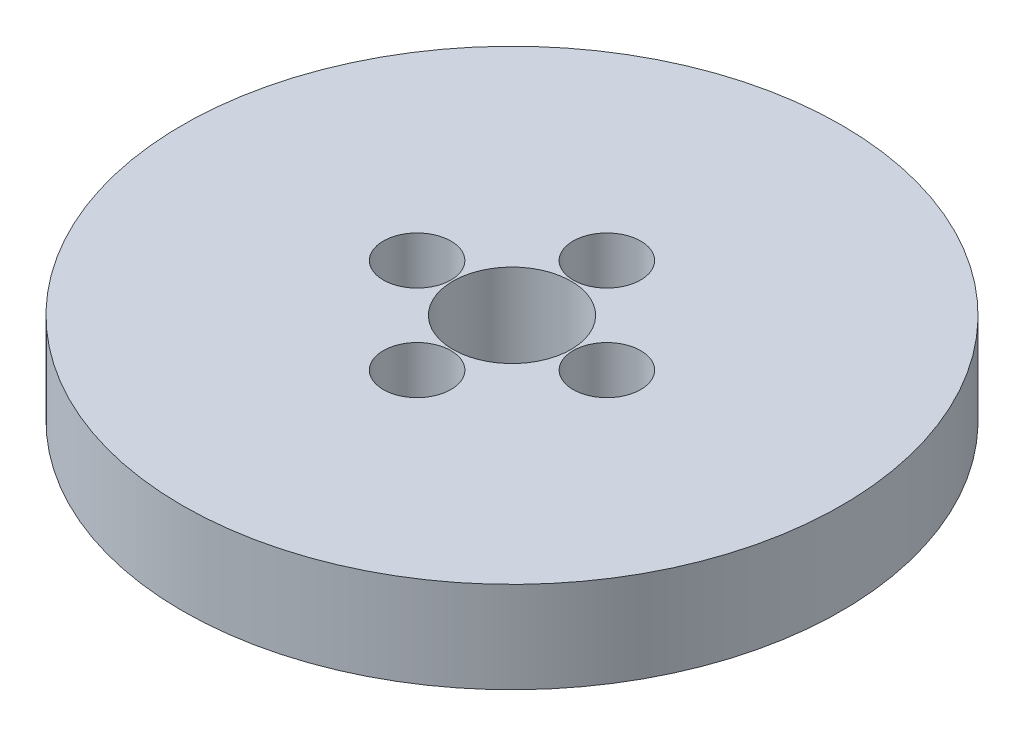
SolidWorks part; units mm, degrees
ref_plane "Front Plane" through (0, 0, 0) normal (0, 0, 1) x (1, 0, 0)
ref_plane "Top Plane" through (0, 0, 0) normal (0, 1, 0) x (1, 0, 0)
ref_plane "Right Plane" through (0, 0, 0) normal (1, 0, 0) x (0, 0, -1)
sketch "Sketch1" plane through (0, 0, 0) normal (0, 1, 0) x (1, 0, 0)
  circle A0 centre (0, 0) radius 97.5
  dimension "FLANGE_OD" = 195
extrude "Boss-Extrude1" add sketch "Sketch1" along normal blind 27
sketch "Sketch2" plane through (0, 0, 0) normal (0, 1, 0) x (1, 0, 0)
  circle A0 centre (0, 0) radius 17.5
  dimension "BORE_D" = 35
extrude "Cut-Extrude1" cut sketch "Sketch2" along normal through all
sketch "Sketch3" plane through (0, 27, 0) normal (0, 1, 0) x (1, 0, 0)
  circle A0 centre (0, 0) radius 28.0745 construction
  circle A1 centre (-28.0745, 0) radius 10
  dimension "BOLT_D" = 20
  dimension "BOLT_PCD" = 56.1489
extrude "Cut-Extrude2" cut sketch "Sketch3" against normal blind 18.6371
pattern_circular "CirPattern1" count 4 over 360 about axis through (0, 0, 0) along (0, 1, 0) of "Cut-Extrude2"
